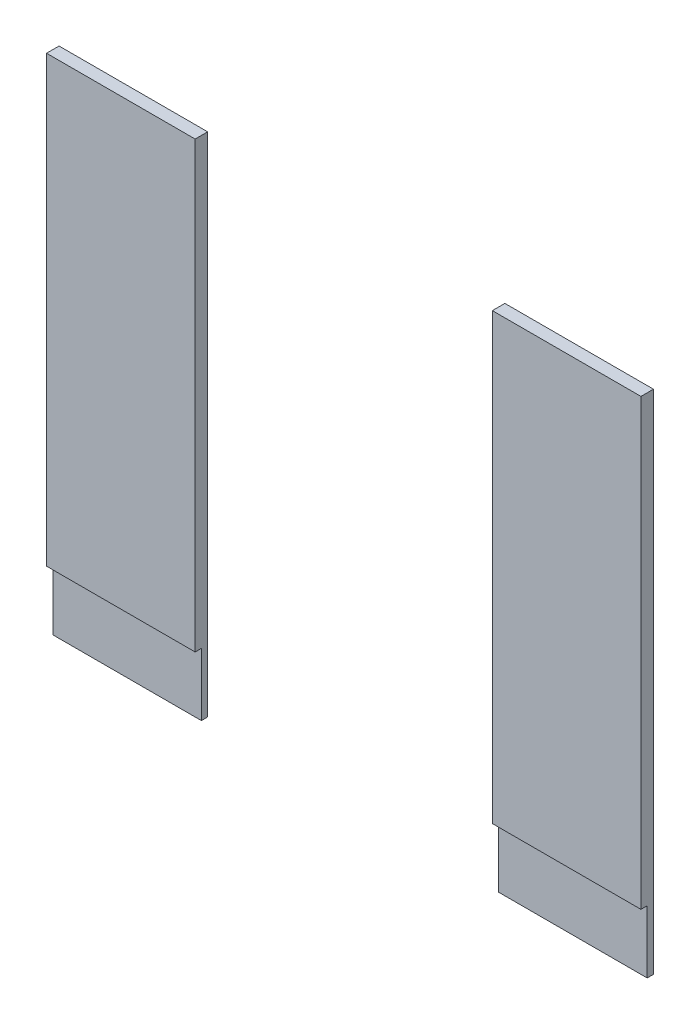
SolidWorks part; units mm, degrees
ref_plane "Front Plane" through (0, 0, 0) normal (0, 0, 1) x (1, 0, 0)
ref_plane "Top Plane" through (0, 0, 0) normal (0, 1, 0) x (1, 0, 0)
ref_plane "Right Plane" through (0, 0, 0) normal (1, 0, 0) x (0, 0, -1)
sketch "Sketch2" plane through (0, 0, 0) normal (0, 0, 1) x (1, 0, 0)
  line L0 (-475, 0) -> (475, 0)
  line L1 (-475, 0) -> (-475, -810)
  line L2 (475, 0) -> (475, -810)
  line L3 (-475, -810) -> (475, -810)
  line L4 (-237.5, 0) -> (-237.5, -810)
  line L5 (237.5, -810) -> (237.5, 0)
  line L6 (475, -243.561) -> (237.5, -243.561) construction
  line L7 (-475, -243.561) -> (-237.5, -243.561) construction
  line L8 (-475, -710) -> (475, -710)
  line L9 (365.1466, -710) -> (365.1466, -810) construction
  point P2 (0, 0)
  dimension "D1" = 237.5
  dimension "D2" = 810
  dimension "D3" = 950
  dimension "D4" = 100
extrude "Boss-Extrude1" add sketch "Sketch2" along normal mid plane 20 contours L4 L0 L1 L3 | L5 L3 L2 L0 region at (-356.25, -355, 0) region at (356.25, -355, 0)
sketch "Sketch3" plane through (0, -710, 0) normal (0, -1, 0) x (1, 0, 0)
  line L0 (-475, 10) -> (-475, -10) construction
  line L1 (-475, 0) -> (-237.5, 0)
  line L2 (-475, 0) -> (-475, -10)
  line L3 (-475, -10) -> (-237.5, -10)
  line L4 (475, 0) -> (475, -10)
  line L5 (-237.5, -10) -> (-237.5, 0)
  line L6 (-237.5, 10) -> (-237.5, -10) construction
  line L7 (237.5, 0) -> (237.5, -10)
  line L8 (237.5, 10) -> (237.5, -10) construction
  line L9 (237.5, -10) -> (475, -10)
  line L10 (237.5, 0) -> (475, 0)
extrude "Boss-Extrude2" add sketch "Sketch3" along normal blind 100
